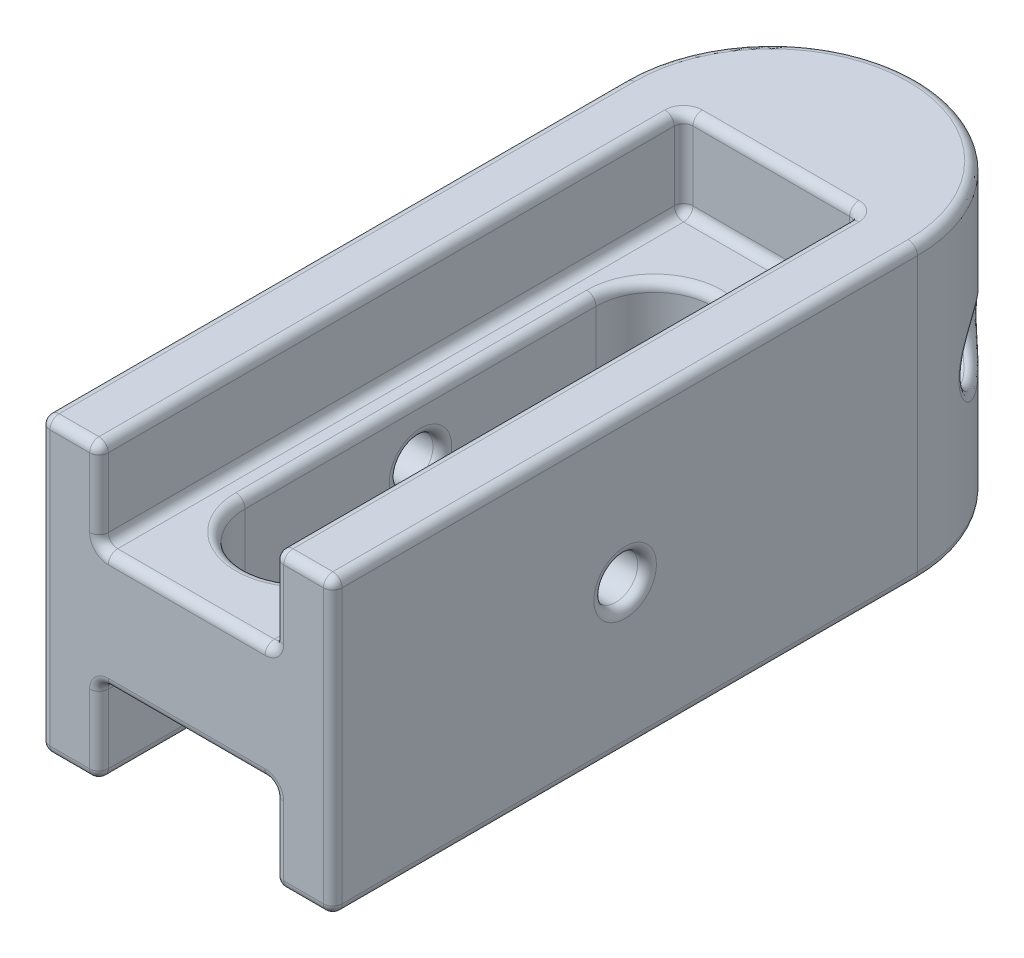
SolidWorks part; units mm, degrees
material "PET"
ref_plane "Front Plane" through (0, 0, 0) normal (0, 0, 1) x (1, 0, 0)
ref_plane "Top Plane" through (0, 0, 0) normal (0, 1, 0) x (1, 0, 0)
ref_plane "Right Plane" through (0, 0, 0) normal (1, 0, 0) x (0, 0, -1)
sketch "Sketch1" plane through (0, 0, 0) normal (0, 0, 1) x (1, 0, 0)
  line L1 (-9.525, 9.525) -> (9.525, 9.525) construction
  line L2 (-9.525, 9.525) -> (-9.525, -9.525) construction
  line L3 (-9.525, -9.525) -> (9.525, -9.525) construction
  line L4 (9.525, 9.525) -> (9.525, -9.525) construction
  line L5 (-9.525, 9.525) -> (9.525, -9.525) construction
  line L6 (-9.525, -9.525) -> (9.525, 9.525) construction
  line L7 (-7.9375, 7.9375) -> (7.9375, 7.9375)
  line L8 (-7.9375, 7.9375) -> (-7.9375, -7.9375)
  line L9 (-7.9375, -7.9375) -> (7.9375, -7.9375)
  line L10 (7.9375, 7.9375) -> (7.9375, -7.9375)
  line L11 (-7.9375, 7.9375) -> (7.9375, -7.9375) construction
  line L12 (-7.9375, -7.9375) -> (7.9375, 7.9375) construction
  point P0 (0, 0)
  point P6 (0, 0)
  dimension "D1" = 19.05
  dimension "D2" = 19.05
  dimension "D3" = 1.5875
extrude "Boss-Extrude1" add sketch "Sketch1" along normal blind 31.75
ref_plane "Plane1" through (0, 0, 0) normal (0, 1, 0) x (1, 0, 0)
sketch "Sketch3" plane through (0, 0, 0) normal (0, 1, 0) x (1, 0, 0)
  line L0 (7.9375, 0) -> (-7.9375, 0) construction
  line L1 (-7.9375, 0) -> (7.9375, 0)
  arc A0 (-7.9375, 0) -> (7.9375, 0) centre (0, 0) cw
extrude "Boss-Extrude3" add sketch "Sketch3" along normal blind 3.175 and the other way blind 3.175
sketch "Sketch4" plane through (7.9375, 0, 0) normal (1, 0, 0) x (0, 0, -1)
  line L0 (-31.75, 0) -> (0, 0) construction
  line L1 (-31.75, -7.9375) -> (-31.75, 7.9375) construction
  line L2 (-15.875, 7.9375) -> (-15.875, -7.9375) construction
  line L3 (-31.75, 7.9375) -> (0, 7.9375) construction
  line L4 (-31.75, -7.9375) -> (0, -7.9375) construction
  line L5 (-31.75, 0) -> (0, 0) construction
  circle A0 centre (-15.875, 0) radius 1.1906
  dimension "D1" = 2.3813
extrude "Cut-Extrude1" cut sketch "Sketch4" against normal through all
sketch "Sketch5" plane through (0, 0, 0) normal (0, 1, 0) x (1, 0, 0)
  line L0 (0, 0) -> (-4.7214, 6.3806)
  line L1 (0, 0) -> (6.3806, 4.7214)
  line L2 (-7.9375, 0) -> (7.9375, 0) construction
  arc A0 (7.9375, 0) -> (-7.9375, 0) centre (0, 0) ccw construction
  dimension "D1" = 53.5
ref_plane "Plane2" through (-4.7214, 0, -6.3806) normal (0.5948, 0, 0.8039) x (0.8039, 0, -0.5948)
sketch "Sketch7" plane through (-4.7214, 0, -6.3806) normal (0.5948, 0, 0.8039) x (0.8039, 0, -0.5948)
  circle A0 centre (0, 0) radius 1.5875
  dimension "D1" = 3.175
ref_plane "Plane3" through (6.3806, 0, -4.7214) normal (0.8039, 0, -0.5948) x (-0.5948, 0, -0.8039)
sketch "Sketch8" plane through (6.3806, 0, -4.7214) normal (0.8039, 0, -0.5948) x (-0.5948, 0, -0.8039)
  circle A0 centre (0, 0) radius 1.5875
  dimension "D1" = 3.175
extrude "Cut-Extrude3" cut sketch "Sketch8" against normal up to vertex (7.9375 mm away) contours A0 up to point (0, 0, 0)
extrude "Cut-Extrude4" cut sketch "Sketch7" along normal up to vertex (7.9375 mm away) contours A0 up to point (0, 0, 0)
sketch "Sketch9" plane through (0, 0, 0) normal (0, 0, -1) x (-1, 0, 0)
  line L0 (-7.9375, 7.9375) -> (7.9375, 7.9375) construction
  line L1 (-4.7625, 7.9375) -> (4.7625, 7.9375)
  line L2 (-4.7625, 7.9375) -> (-4.7625, 3.175)
  line L3 (-4.7625, 3.175) -> (4.7625, 3.175)
  line L4 (4.7625, 7.9375) -> (4.7625, 3.175)
  line L5 (7.9375, 3.175) -> (-7.9375, 3.175) construction
  line L6 (-7.9375, 3.175) -> (-7.9375, 7.9375) construction
  line L7 (7.9375, 7.9375) -> (7.9375, 3.175) construction
  line L8 (-7.9375, 0) -> (7.9375, 0) construction
  line L9 (-7.9375, -3.175) -> (-7.9375, 3.175) construction
  line L10 (7.9375, -3.175) -> (7.9375, 3.175) construction
  line L11 (-4.7625, -7.9375) -> (4.7625, -7.9375)
  line L12 (-4.7625, -3.175) -> (4.7625, -3.175)
  line L13 (4.7625, -7.9375) -> (4.7625, -3.175)
  line L14 (-4.7625, -7.9375) -> (-4.7625, -3.175)
  dimension "D1" = 3.175
  dimension "D2" = 3.175
extrude "Cut-Extrude5" cut sketch "Sketch9" against normal through all
sketch "Sketch10" plane through (0, -3.175, 0) normal (0, -1, 0) x (-1, 0, 0)
  line L0 (0, -31.75) -> (0, 0) construction
  line L1 (4.7625, -31.75) -> (-4.7625, -31.75) construction
  line L2 (0, -25.4) -> (0, -6.35) construction
  line L3 (-3.175, -25.4) -> (-3.175, -6.35)
  line L4 (3.175, -25.4) -> (3.175, -6.35)
  arc A0 (-3.175, -25.4) -> (3.175, -25.4) centre (0, -25.4) ccw
  arc A1 (3.175, -6.35) -> (-3.175, -6.35) centre (0, -6.35) ccw
  point P7 (0, -15.875)
  dimension "D1" = 6.35
  dimension "D2" = 6.35
extrude "Cut-Extrude6" cut sketch "Sketch10" against normal through all
fillet "Fillet1" radius 0.508 2 edges at (7.181, -0.33, -3.3819) (-3.3819, 0.33, -7.181)
fillet "Fillet14" radius 0.508 4 edges at (3.175, 0, 14.6844) (7.9375, 0, 14.6844) (-3.175, 0, 17.0656) (-7.9375, 0, 14.6844)
sketch "Sketch13" plane through (0, 3.175, 0) normal (0, 1, 0) x (1, 0, 0)
  line L0 (-7.9375, 0) -> (7.9375, 0)
  arc A0 (7.9375, 0) -> (-7.9375, 0) centre (0, 0) ccw
extrude "Boss-Extrude14" add sketch "Sketch13" along normal blind 4.7625
mirror "Mirror1" about plane through (0, 0, 0) normal (0, 1, 0) of "Boss-Extrude14"
fillet "Fillet15" radius 0.508 42 edges at (-4.7625, -5.5563, 0) (4.7625, -5.5563, 0) (-3.175, -3.175, 15.875) (0, -3.175, 3.175) (3.175, -3.175, 15.875) (0, -3.175, 28.575) (-4.7625, -3.175, 15.875) (4.7625, -3.175, 15.875) (0, -3.175, 0) (-4.7625, -7.9375, 15.875) (0, -7.9375, 0) (4.7625, -7.9375, 15.875) (7.9375, -7.9375, 15.875) (0, -7.9375, -7.9375) (-7.9375, -7.9375, 15.875) (6.35, -7.9375, 31.75) (4.7625, -5.5563, 31.75) (0, -3.175, 31.75) (-4.7625, -5.5563, 31.75) (-6.35, -7.9375, 31.75) (-7.9375, 0, 31.75) (-4.7625, 5.5563, 31.75) (-4.7625, 5.5563, 0) (4.7625, 5.5563, 0) (4.7625, 3.175, 15.875) (0, 3.175, 31.75) (-4.7625, 3.175, 15.875) (0, 3.175, 0) (0, 3.175, 3.175) (-3.175, 3.175, 15.875) (0, 3.175, 28.575) (3.175, 3.175, 15.875) (-7.9375, 7.9375, 15.875) (0, 7.9375, -7.9375) (7.9375, 7.9375, 15.875) (4.7625, 7.9375, 15.875) (0, 7.9375, 0) (-4.7625, 7.9375, 15.875) (-6.35, 7.9375, 31.75) (7.9375, 0, 31.75) (4.7625, 5.5563, 31.75) (6.35, 7.9375, 31.75)
equation "\"0..015in\"=0.625"
